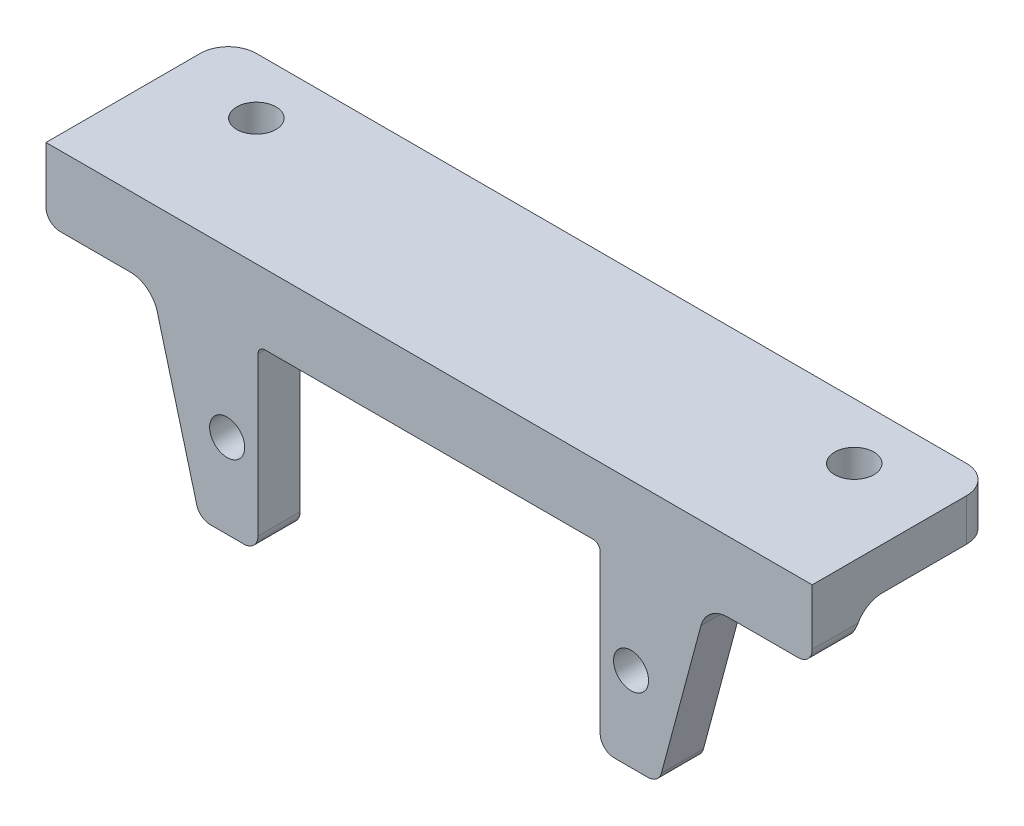
SolidWorks part; units mm, degrees
ref_plane "Front Plane" through (0, 0, 0) normal (0, 0, 1) x (1, 0, 0)
ref_plane "Top Plane" through (0, 0, 0) normal (0, 1, 0) x (1, 0, 0)
ref_plane "Right Plane" through (0, 0, 0) normal (1, 0, 0) x (0, 0, -1)
sketch "Sketch1" plane through (0, 0, 0) normal (0, 0, 1) x (1, 0, 0)
  line L1 (-15.9, -6.25) -> (15.9, -6.25)
  line L2 (-15.9, -6.25) -> (-15.9, 6.25)
  line L3 (-15.9, 6.25) -> (15.9, 6.25)
  line L4 (15.9, -6.25) -> (15.9, 6.25)
  line L5 (-15.9, -6.25) -> (15.9, 6.25) construction
  line L6 (-15.9, 6.25) -> (15.9, -6.25) construction
  line L7 (11.7, -6.25) -> (-11.7, -6.25)
  line L8 (11.7, -6.25) -> (11.7, 6.25)
  line L9 (11.7, 6.25) -> (-11.7, 6.25)
  line L10 (-11.7, -6.25) -> (-11.7, 6.25)
  line L11 (11.7, -6.25) -> (-11.7, 6.25) construction
  line L12 (11.7, 6.25) -> (-11.7, -6.25) construction
  circle A0 centre (-14.4, 0) radius 1
  circle A1 centre (-14.4, 3.5) radius 1
  circle A2 centre (-14.4, -3.5) radius 1
  circle A3 centre (14.4, 0) radius 1
  circle A4 centre (14.4, 3.5) radius 1
  circle A5 centre (14.4, -3.5) radius 1
  point P0 (0, 0)
  point P14 (0, 0)
  point P17 (0, 0)
  point P20 (0, 0)
  dimension "D3" = 2
  dimension "D1" = 31.8
  dimension "D2" = 12.5
  dimension "D4" = 1.5
  dimension "D5" = 3.5
  dimension "D6" = 3.5
  dimension "D7" = 1.5
  dimension "D8" = 23.4
sketch "Sketch3" plane through (0, 0, 0) normal (0, 0, 1) x (1, 0, 0)
  line L0 (-12.2, 6.25) -> (-12.2, -5)
  line L1 (-11.7, -6.25) -> (-11.7, 6.25) construction
  line L2 (-13.2, -6) -> (-15.6, -6)
  line L3 (-16.5659, -5.2588) -> (-19.3865, 5.2676)
  line L4 (12.2, 6.25) -> (12.2, -5)
  line L5 (11.7, -6.25) -> (11.7, 6.25) construction
  line L6 (13.2, -6) -> (15.6, -6)
  line L7 (16.5659, -5.2588) -> (19.3865, 5.2676)
  line L8 (-11.7, 6.75) -> (11.7, 6.75)
  line L9 (-15.9, 6.25) -> (15.9, 6.25) construction
  line L12 (-27.3183, 11.75) -> (27.3183, 11.75)
  line L14 (-21.3183, 6.75) -> (-26.3183, 6.75)
  line L15 (-27.3183, 7.75) -> (-27.3183, 11.75)
  line L16 (21.3183, 6.75) -> (26.3183, 6.75)
  line L17 (27.3183, 7.75) -> (27.3183, 11.75)
  circle A0 centre (-14.4, 0) radius 1.25
  circle A1 centre (14.4, 0) radius 1.25
  arc A2 (-12.2, -5) -> (-13.2, -6) centre (-13.2, -5) cw
  arc A3 (-15.6, -6) -> (-16.5659, -5.2588) centre (-15.6, -5) cw
  arc A4 (13.2, -6) -> (12.2, -5) centre (13.2, -5) cw
  arc A5 (16.5659, -5.2588) -> (15.6, -6) centre (15.6, -5) cw
  arc A6 (-11.7, 6.75) -> (-12.2, 6.25) centre (-11.7, 6.25) ccw
  arc A7 (12.2, 6.25) -> (11.7, 6.75) centre (11.7, 6.25) ccw
  arc A8 (-19.3865, 5.2676) -> (-21.3183, 6.75) centre (-21.3183, 4.75) ccw
  arc A9 (21.3183, 6.75) -> (19.3865, 5.2676) centre (21.3183, 4.75) ccw
  arc A10 (-26.3183, 6.75) -> (-27.3183, 7.75) centre (-26.3183, 7.75) cw
  arc A11 (27.3183, 7.75) -> (26.3183, 6.75) centre (26.3183, 7.75) cw
  point P16 (14.4, -6)
  point P22 (-12.2, -6)
  point P25 (-16.3673, -6)
  point P27 (-14.4, -6)
  point P30 (12.2, -6)
  point P40 (0, 0)
  point P42 (0, 0)
  point P43 (0, 0)
  point P46 (-19.7837, 6.75)
  point P49 (19.7837, 6.75)
  dimension "D1" = 2.5
  dimension "D9" = 1
  dimension "D10" = 1
  dimension "D11" = 1
  dimension "D6" = 1
  dimension "D12" = 0.5
  dimension "D13" = 0.5
  dimension "D14" = 2
  dimension "D15" = 2
  dimension "D16" = 1
  dimension "D17" = 1
  dimension "D2" = 0.5
  dimension "D3" = 75
  dimension "D4" = 0.5
  dimension "D8" = 0.5
  dimension "D5" = 6
  dimension "D7" = 75
  dimension "D18" = 5
  dimension "D19" = 5
extrude "Boss-Extrude1" add sketch "Sketch3" along normal blind 3
sketch "Sketch4" plane through (0, 0, 0) normal (0, 0, -1) x (-1, 0, 0)
  line L2 (27.3183, 11.75) -> (27.3183, 7.75) construction
  line L3 (-27.3183, 11.75) -> (27.3183, 11.75)
  line L4 (-27.3183, 11.75) -> (-27.3183, 8.75)
  line L5 (-27.3183, 8.75) -> (27.3183, 8.75)
  line L6 (27.3183, 11.75) -> (27.3183, 8.75)
  point P1 (0, 0)
  point P2 (0, 0)
  point P9 (-27.3183, 8.75)
  point P12 (27.3183, 8.75)
  dimension "D1" = 3
extrude "Boss-Extrude2" add sketch "Sketch4" along normal blind 10
fillet "Fillet1" radius 2 1 edges at (0, 8.75, 0)
fillet "Fillet2" radius 2 2 edges at (-27.3183, 10.25, -10) (27.3183, 10.25, -10)
sketch "Sketch5" plane through (0, 8.75, 0) normal (0, -1, 0) x (1, 0, 0)
  line L0 (-27.3183, -8) -> (-27.3183, -2) construction
  line L2 (25.3183, -10) -> (-25.3183, -10) construction
  circle A0 centre (-21.3183, -6) radius 1.4
  point P2 (-18.3573, -5.9078)
  dimension "D1" = 2.8
  dimension "D2" = 6
  dimension "D3" = 4
extrude "Cut-Extrude1" cut sketch "Sketch5" against normal through all
mirror "Mirror1" about plane through (0, 0, 0) normal (1, 0, 0) of "Cut-Extrude1"
equation "\"D6@Sketch1\"=\"D5@Sketch1\""
equation "\"D7@Sketch1\"=\"D4@Sketch1\""
equation "\"D4@Sketch3\"=\"D2@Sketch3\""
equation "\"D8@Sketch3\"=\"D2@Sketch3\""
